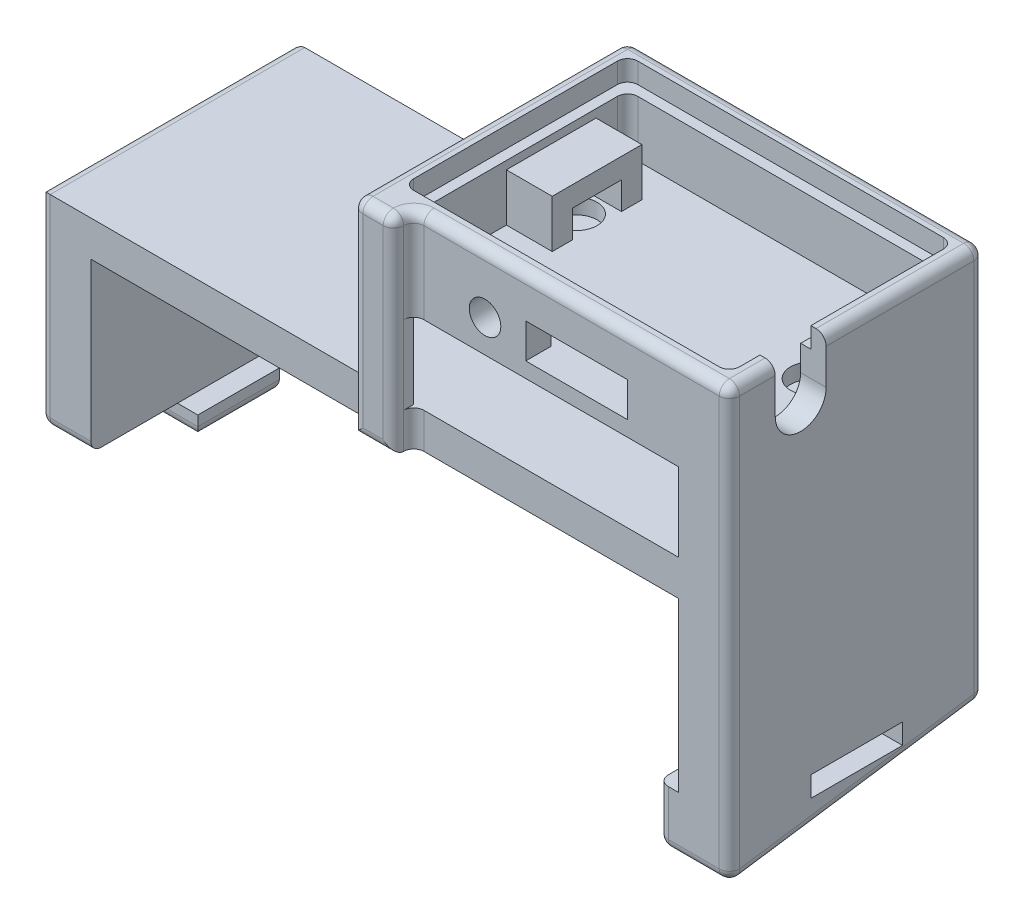
SolidWorks part; units mm, degrees
ref_plane "Front Plane" through (0, 0, 0) normal (0, 0, 1) x (1, 0, 0)
ref_plane "Top Plane" through (0, 0, 0) normal (0, 1, 0) x (1, 0, 0)
ref_plane "Right Plane" through (0, 0, 0) normal (1, 0, 0) x (0, 0, -1)
sketch "Sketch1" plane through (0, 0, 0) normal (0, 0, 1) x (1, 0, 0)
  line L0 (0, 0) -> (30, 0)
  line L1 (30, 0) -> (30, -7.7)
  line L2 (30, -7.7) -> (-32.7, -7.7)
  line L3 (-32.7, -7.7) -> (-32.7, -27.7)
  line L4 (-32.7, -27.7) -> (35, -27.7)
  line L5 (35, -27.7) -> (35, 9)
  line L6 (35, 9) -> (0, 9)
  line L7 (0, 9) -> (0, 0)
  dimension "D1" = 7.7
  dimension "D2" = 30
  dimension "D3" = 35
  dimension "D4" = 67.7
  dimension "D5" = 9
  dimension "D6" = 20
extrude "Boss-Extrude1" add sketch "Sketch1" along normal blind 25
sketch "Sketch2" plane through (0, 0, 25) normal (0, 0, 1) x (1, 0, 0)
  line L0 (-32.7, -27.7) -> (35, -27.7) construction
  line L1 (30, -27.7) -> (-27.7, -27.7)
  line L2 (30, -27.7) -> (30, -11.2)
  line L3 (30, -11.2) -> (-27.7, -11.2)
  line L4 (-27.7, -27.7) -> (-27.7, -11.2)
  line L5 (35, -27.7) -> (35, 9) construction
  dimension "D1" = 57.7
  dimension "D2" = 5
  dimension "D3" = 16.5
extrude "Cut-Extrude1" cut sketch "Sketch2" against normal through all
sketch "Sketch3" plane through (0, 9, 0) normal (0, 1, 0) x (1, 0, 0)
  line L0 (35, -25) -> (35, 0) construction
  line L1 (2.5, -2.5) -> (32.5, -2.5)
  line L2 (2.5, -2.5) -> (2.5, -22.5)
  line L3 (2.5, -22.5) -> (32.5, -22.5)
  line L4 (32.5, -2.5) -> (32.5, -22.5)
  line L5 (0, -25) -> (0, 0) construction
  line L6 (35, 0) -> (0, 0) construction
  line L7 (35, -25) -> (0, -25) construction
  dimension "D1" = 2.5
  dimension "D2" = 2.5
  dimension "D3" = 2.5
  dimension "D4" = 2.5
extrude "Cut-Extrude2" cut sketch "Sketch3" against normal blind 7.5
sketch "Sketch4" plane through (0, -27.7, 0) normal (0, -1, 0) x (1, 0, 0)
  line L0 (35, 12.5) -> (35.1733, 12.5) construction
  line L1 (35, 25) -> (35, 0) construction
  line L2 (30, 0) -> (30, 25) construction
  circle A0 centre (30.5, 12.5) radius 2
  dimension "D1" = 4
  dimension "D2" = 0.5
extrude "Cut-Extrude3" cut sketch "Sketch4" against normal up to surface (29.2 mm away) up to face at (17.5, 1.5, 12.5)
sketch "Sketch5" plane through (0, 1.5, 0) normal (0, 1, 0) x (1, 0, 0)
  line L0 (35, -25) -> (0, -25) construction
  line L2 (30, -25) -> (30, -14.4365) construction
  circle A0 centre (5, -10) radius 2
  dimension "D1" = 4
  dimension "D2" = 25
  dimension "D3" = 15
extrude "Cut-Extrude4" cut sketch "Sketch5" against normal up to surface (1.5 mm away) up to face at (19.75, 0, 12.5)
sketch "Sketch6" plane through (0, -27.7, 0) normal (0, -1, 0) x (1, 0, 0)
  line L0 (35, 25) -> (35, 0) construction
  line L1 (35, 25) -> (28, 25)
  line L2 (35, 25) -> (35, 17)
  line L3 (35, 17) -> (28, 17)
  line L4 (28, 25) -> (28, 17)
  line L5 (35, 0) -> (28, 0)
  line L6 (35, 0) -> (35, 8)
  line L7 (35, 8) -> (28, 8)
  line L8 (28, 0) -> (28, 8)
  line L9 (-32.7, 25) -> (-32.7, 0) construction
  line L10 (-32.7, 16.5) -> (-25.7, 16.5)
  line L11 (-32.7, 16.5) -> (-32.7, 8.5)
  line L12 (-32.7, 8.5) -> (-25.7, 8.5)
  line L13 (-25.7, 16.5) -> (-25.7, 8.5)
  line L14 (35, 12.5) -> (36.5966, 12.5) construction
  dimension "D1" = 8
  dimension "D2" = 7
extrude "Boss-Extrude2" add sketch "Sketch6" along normal blind 2
sketch "Sketch7" plane through (0, 0, 25) normal (0, 0, 1) x (1, 0, 0)
  line L0 (0, 9) -> (0, -11.2)
  line L1 (35, 9) -> (0, 9) construction
  line L3 (30, -11.2) -> (-27.7, -11.2) construction
  line L4 (4, -11.2) -> (4, 9)
  line L5 (4, 9) -> (0, 9)
  line L20 (30, -11.2) -> (30, -27.7)
  line L21 (30, -27.7) -> (28, -27.7)
  line L22 (28, -27.7) -> (28, -29.7)
  line L23 (28, -29.7) -> (35, -29.7)
  line L24 (35, -29.7) -> (35, 9)
  line L25 (35, 9) -> (0, 9)
  line L26 (0, 9) -> (0, 0)
  line L27 (0, 0) -> (30, 0)
  line L28 (30, 0) -> (30, -7.7)
  line L29 (30, -7.7) -> (-32.7, -7.7)
  line L30 (-32.7, -7.7) -> (-32.7, -27.7)
  line L31 (-32.7, -27.7) -> (-27.7, -27.7)
  line L32 (-27.7, -27.7) -> (-27.7, -11.2)
  line L33 (-27.7, -11.2) -> (30, -11.2)
  line L47 (0, -11.2) -> (4, -11.2)
  dimension "D2" = 4
  dimension "D1" = 0
extrude "Boss-Extrude3" add sketch "Sketch7" along normal blind 2
sketch "Sketch8" plane through (35, 0, 0) normal (1, 0, 0) x (0, 0, -1)
  line L0 (0, -29.7) -> (-25, -33.3607)
  line L2 (-25, -33.3607) -> (-25, -29.7)
  line L3 (-25, -29.7) -> (-25, 9) construction
  line L4 (-25, -29.7) -> (0, -29.7)
  line L5 (0, -29.7) -> (-8, -29.7) construction
  dimension "D1" = 8.331
  dimension "D2" = 3.6607
extrude "Boss-Extrude4" add sketch "Sketch8" against normal up to surface (7 mm away) up to face at (28, -28.7, 4)
sketch "Sketch9" plane through (0, 9, 0) normal (0, 1, 0) x (1, 0, 0)
  line L0 (32.5, -22.5) -> (32.5, -2.5) construction
  line L1 (33.5, -23.5) -> (1.5, -23.5)
  line L2 (33.5, -23.5) -> (33.5, -1.5)
  line L3 (33.5, -1.5) -> (1.5, -1.5)
  line L4 (1.5, -23.5) -> (1.5, -1.5)
  line L5 (2.5, -22.5) -> (32.5, -22.5) construction
  line L6 (2.5, -2.5) -> (2.5, -22.5) construction
  line L7 (32.5, -2.5) -> (2.5, -2.5) construction
  dimension "D1" = 1
  dimension "D2" = 1
  dimension "D3" = 1
  dimension "D4" = 1
extrude "Cut-Extrude5" cut sketch "Sketch9" against normal blind 2
fillet "Fillet1" radius 1 8 edges at (33.5, 8, 1.5) (1.5, 8, 1.5) (1.5, 8, 23.5) (33.5, 8, 23.5) (32.5, 4.25, 2.5) (2.5, 4.25, 2.5) (2.5, 4.25, 22.5) (32.5, 4.25, 22.5)
fillet "Fillet2" radius 1 34 edges at (0, 9, 13.5) (17.5, 9, 0) (35, 9, 12.5) (28, -30.5304, 25) (28, -28.7, 0) (28, -31.5304, 12.5) (35, -31.5304, 12.5) (-30.2, -27.7, 0) (-30.2, -27.7, 25) (-29.2, -29.7, 8.5) (-29.2, -29.7, 16.5) (-32.7, -28.7, 8.5) (-32.7, -28.7, 16.5) (-32.7, -27.7, 20.75) (-32.7, -29.7, 12.5) (-32.7, -27.7, 4.25) (-32.7, -7.7, 12.5) (-32.7, -17.7, 0) (-32.7, -17.7, 25) (35, -10.35, 0) (35, -12.1804, 25) (0, -1.1, 27) (0, 4.5, 0) (4, -1.1, 27) (2, -11.2, 27) (2, 9, 27) (31.5, -33.3607, 25) (31.5, -29.7, 0) (-25.7, -29.7, 12.5)
sketch "Sketch10" plane through (-27.7, 0, 0) normal (1, 0, 0) x (0, 0, -1)
  line L0 (-12.5, -11.2) -> (-12.5, -2.753) construction
  line L1 (0, -11.2) -> (-25, -11.2) construction
  circle A0 centre (-14, -13.55) radius 1
  circle A1 centre (-11, -13.55) radius 1
  dimension "D2" = 2
  dimension "D3" = 2
  dimension "D1" = 3
  dimension "D4" = 2.35
extrude "Boss-Extrude5" add sketch "Sketch10" along normal blind 1.5
fillet "Fillet3" radius 1 2 edges at (-26.2, -13.55, 13) (-26.2, -13.55, 10)
sketch "Sketch11" plane through (0, 1.5, 0) normal (0, 1, 0) x (1, 0, 0)
  line L0 (2.5, -5.6) -> (2.5, -14.4)
  line L1 (2.5, -21.5) -> (2.5, -3.5) construction
  line L2 (2.5, -14.4) -> (7, -14.4)
  line L3 (7, -14.4) -> (7, -12.4)
  line L4 (7, -12.4) -> (3, -12.4)
  line L5 (3, -12.4) -> (3, -7.6)
  line L6 (3, -7.6) -> (7, -7.6)
  line L7 (7, -7.6) -> (7, -5.6)
  line L8 (7, -5.6) -> (2.5, -5.6)
  line L9 (5, -10) -> (10.1114, -10) construction
  dimension "D1" = 2
  dimension "D2" = 2
  dimension "D3" = 0.5
  dimension "D4" = 4.5
  dimension "D5" = 4.8
extrude "Boss-Extrude6" add sketch "Sketch11" along normal blind 2.7
sketch "Sketch12" plane through (35, 0, 0) normal (1, 0, 0) x (0, 0, -1)
  line L0 (-20.5, 9) -> (-20.5, 4.5)
  line L1 (-24, 9) -> (-1, 9) construction
  line L2 (-15.5, 4.5) -> (-15.5, 9)
  line L3 (-15.5, 9) -> (-20.5, 9)
  line L4 (-25, 8) -> (-25, 0) construction
  arc A0 (-20.5, 4.5) -> (-15.5, 4.5) centre (-18, 4.5) ccw
  dimension "D1" = 2.5
  dimension "D2" = 4.5
  dimension "D3" = 7
extrude "Cut-Extrude6" cut sketch "Sketch12" against normal up to surface (2.5 mm away) up to face at (32.5, 3.7, 12.5)
sketch "Sketch13" plane through (0, 4.2, 0) normal (0, 1, 0) x (1, 0, 0)
  line L1 (7, -5.6) -> (2.5, -5.6)
  line L2 (7, -5.6) -> (7, -14.4)
  line L3 (7, -14.4) -> (2.5, -14.4)
  line L4 (2.5, -5.6) -> (2.5, -14.4)
extrude "Boss-Extrude7" add sketch "Sketch13" along normal blind 2
sketch "Sketch14" plane through (0, 0, 22.5) normal (0, 0, -1) x (-1, 0, 0)
  line L0 (-3.5, 1.5) -> (-31.5, 1.5) construction
  line L1 (-25, 1.5) -> (-15, 1.5)
  line L2 (-25, 1.5) -> (-25, 4.9)
  line L3 (-25, 4.9) -> (-15, 4.9)
  line L4 (-15, 1.5) -> (-15, 4.9)
  line L5 (-35, -28.8358) -> (-35, 8) construction
  dimension "D1" = 3.4
  dimension "D2" = 10
  dimension "D3" = 10
extrude "Cut-Extrude7" cut sketch "Sketch14" against normal through all
sketch "Sketch15" plane through (0, 0, 25) normal (0, 0, 1) x (1, 0, 0)
  line L0 (15, 3.2) -> (16.3669, 3.2) construction
  line L1 (15, 4.9) -> (15, 1.5) construction
  circle A0 centre (11, 3.2) radius 1.55
  dimension "D1" = 3.1
  dimension "D2" = 4
extrude "Cut-Extrude8" cut sketch "Sketch15" against normal up to surface (2.5 mm away) up to face at (18.75, 3.725, 22.5)
